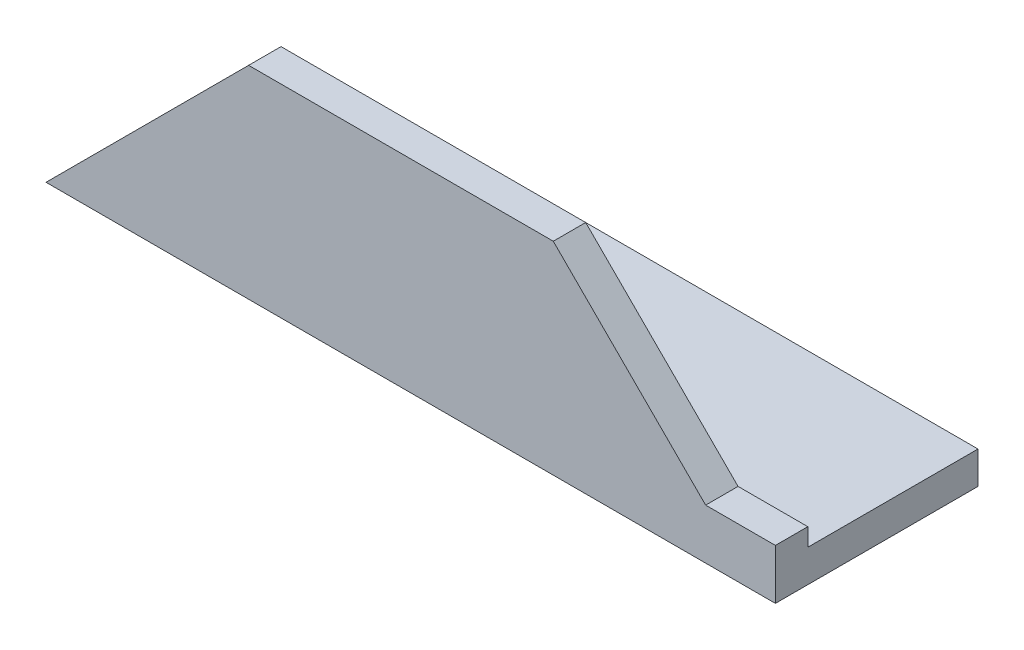
SolidWorks part; units mm, degrees
ref_plane "Спереди" through (0, 0, 0) normal (0, 0, 1) x (1, 0, 0)
ref_plane "Сверху" through (0, 0, 0) normal (0, 1, 0) x (1, 0, 0)
ref_plane "Справа" through (0, 0, 0) normal (1, 0, 0) x (0, 0, -1)
sketch "Эскиз1" plane through (0, 0, 0) normal (1, 0, 0) x (0, 0, -1)
  line L0 (0, 0) -> (25, 0)
  line L1 (0, 0) -> (0, 25)
extrude "Вытянуть-Тонкостенный1" add sketch "Эскиз1" along normal blind 90 thin thin type one direction wall 4
sketch "Эскиз2" plane through (0, 0, 0) normal (0, 0, 1) x (1, 0, 0)
  line L0 (0, 0) -> (0, 25)
  line L1 (0, 25) -> (25, 25)
  line L2 (90, 25) -> (0, 25) construction
  line L3 (25, 25) -> (0, 0)
  line L4 (90, 6.1993) -> (81.3946, 6.1993)
  line L5 (62.5939, 25) -> (90, 25)
  line L6 (90, 25) -> (90, 6.1993)
  line L9 (81.3946, 6.1993) -> (62.5939, 25)
extrude "Вырез-Вытянуть1" cut sketch "Эскиз2" against normal through all
